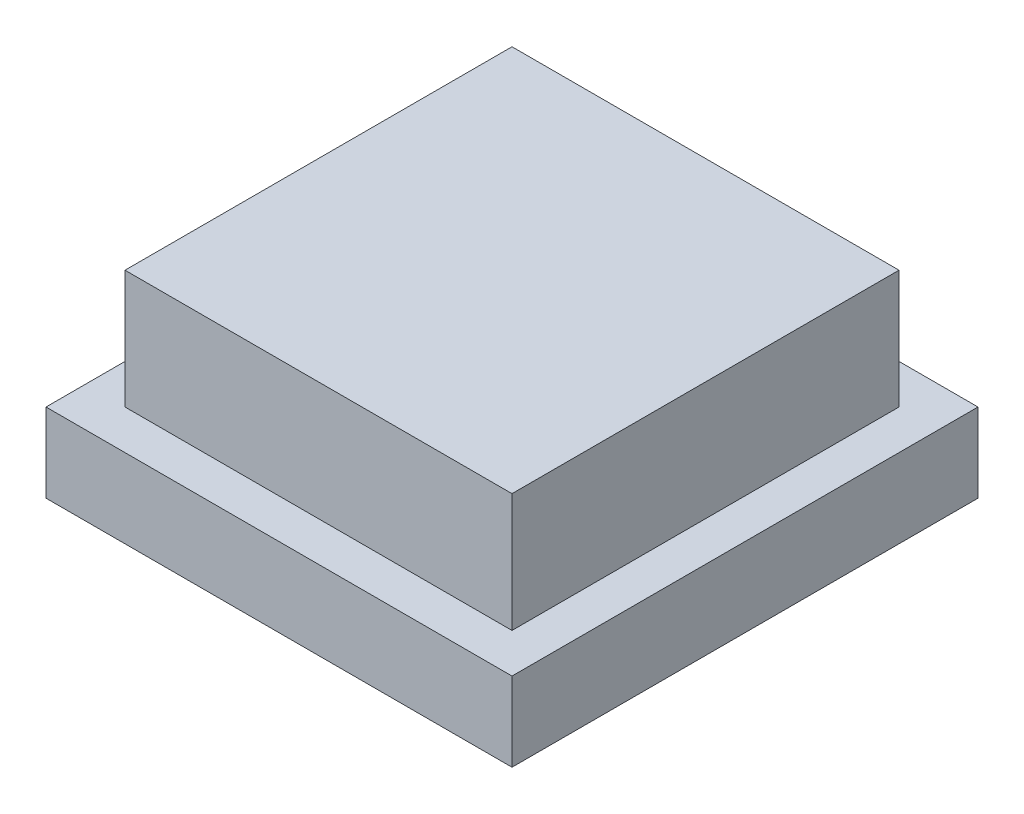
SolidWorks part; units mm, degrees
ref_plane "Front Plane" through (0, 0, 0) normal (0, 0, 1) x (1, 0, 0)
ref_plane "Top Plane" through (0, 0, 0) normal (0, 1, 0) x (1, 0, 0)
ref_plane "Right Plane" through (0, 0, 0) normal (1, 0, 0) x (0, 0, -1)
sketch "Sketch1" plane through (0, 0, 0) normal (0, 1, 0) x (1, 0, 0)
  line L0 (4.1102, 4.4563) -> (-7.6898, 4.4563)
  line L1 (3.1102, -6.3437) -> (-6.6898, -6.3437)
  line L2 (3.1102, -6.3437) -> (3.1102, 3.4563)
  line L3 (3.1102, 3.4563) -> (-6.6898, 3.4563)
  line L4 (-6.6898, -6.3437) -> (-6.6898, 3.4563)
  line L5 (-7.6898, -7.3437) -> (-7.6898, 4.4563)
  line L6 (4.1102, -7.3437) -> (-7.6898, -7.3437)
  line L7 (4.1102, -7.3437) -> (4.1102, 4.4563)
  point P0 (0, 0)
  dimension "D1" = 1
extrude "Boss-Extrude4" add sketch "Sketch1" along normal blind 5 contours L4 L1 L2 L3 region at (-1.7898, 0, 1.4437)
extrude "Boss-Extrude5" add sketch "Sketch1<4>" along normal blind 2
sketch "Sketch1<4>" plane through (0, 0, 0) normal (0, 1, 0) x (1, 0, 0) same geometry as "Sketch1"
